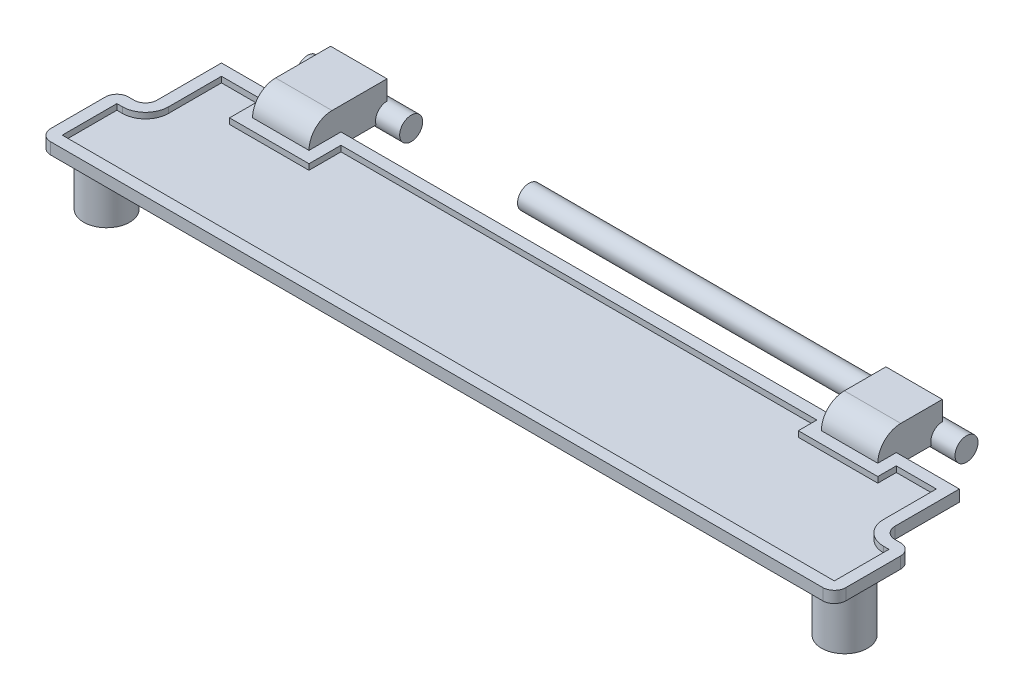
SolidWorks part; units mm, degrees
material "Alloy Steel"
ref_plane "Front Plane" through (0, 0, 0) normal (0, 0, 1) x (1, 0, 0)
ref_plane "Top Plane" through (0, 0, 0) normal (0, 1, 0) x (1, 0, 0)
ref_plane "Right Plane" through (0, 0, 0) normal (1, 0, 0) x (0, 0, -1)
sketch "Sketch1" plane through (0, 0, 0) normal (0, 1, 0) x (1, 0, 0)
  line L0 (0, 0) -> (64.1, 0) construction
  circle A0 centre (64.1, 0) radius 2
  circle A1 centre (0, 0) radius 2
extrude "Boss-Extrude1" add sketch "Sketch1" along normal blind 5
sketch "Sketch2" plane through (0, 5, 0) normal (0, 1, 0) x (1, 0, 0)
  line L0 (0, 0) -> (0, 16.0284) construction
  line L1 (0, 16.0284) -> (64.1, 16.0284) construction
  line L2 (64.1, 16.0284) -> (64.1, -7.5811) construction
  line L3 (0, 3.3731) -> (0, 9.9731)
  line L4 (0, 9.9731) -> (64.1, 9.9731)
  line L5 (64.1, 3.3731) -> (64.1, 9.9731)
  line L6 (66.5854, -3.3731) -> (-2.4854, -3.3731)
  line L7 (66.5854, -3.3731) -> (66.5854, 3.3731)
  line L8 (66.5854, 3.3731) -> (64.1, 3.3731)
  line L9 (-2.4854, -3.3731) -> (-2.4854, 3.3731)
  line L10 (-7.3374, 0) -> (72.8127, 0) construction
  line L12 (0, 3.3731) -> (-2.4854, 3.3731)
  point P4 (32.05, 0)
  point P7 (32.05, 0)
  dimension "D1" = 64.1
extrude "Boss-Extrude3" add sketch "Sketch2" along normal blind 1
fillet "Fillet1" radius 1 6 edges at (0, 5.5, -3.3731) (64.1, 5.5, -3.3731) (66.5854, 5.5, -3.3731) (66.5854, 5.5, 3.3731) (-2.4854, 5.5, 3.3731) (-2.4854, 5.5, -3.3731)
sketch "Sketch3" plane through (0, 6, 0) normal (0, 1, 0) x (1, 0, 0)
  line L0 (32.05, 9.9731) -> (3.43, 9.9731) construction
  line L1 (64.1, 9.9731) -> (0, 9.9731) construction
  line L2 (32.05, 9.9731) -> (60.67, 9.9731) construction
  line L3 (3.43, 9.9731) -> (3.43, 13.9731) construction
  line L4 (3.43, 13.9731) -> (12.43, 13.9731) construction
  line L5 (60.67, 9.9731) -> (60.67, 13.9731) construction
  line L6 (60.67, 13.9731) -> (51.67, 13.9731) construction
  line L7 (7.93, 13.9731) -> (7.93, 7.1953) construction
  line L8 (56.17, 13.9731) -> (56.17, 8.3637) construction
  line L9 (12.43, 13.9731) -> (50.1115, 13.9731) construction
  line L10 (5.48, 7.1953) -> (10.38, 7.1953)
  line L11 (5.48, 7.1953) -> (5.48, 13.9731)
  line L12 (5.48, 13.9731) -> (10.38, 13.9731)
  line L13 (10.38, 7.1953) -> (10.38, 13.9731)
  line L14 (5.48, 7.1953) -> (10.38, 13.9731) construction
  line L15 (5.48, 13.9731) -> (10.38, 7.1953) construction
  line L16 (58.62, 8.3637) -> (53.72, 8.3637)
  line L17 (58.62, 8.3637) -> (58.62, 13.9731)
  line L18 (58.62, 13.9731) -> (53.72, 13.9731)
  line L19 (53.72, 8.3637) -> (53.72, 13.9731)
  line L20 (58.62, 8.3637) -> (53.72, 13.9731) construction
  line L21 (58.62, 13.9731) -> (53.72, 8.3637) construction
  point P13 (7.93, 10.5842)
  point P18 (56.17, 11.1684)
  dimension "D1" = 28.62
extrude "Boss-Extrude4" add sketch "Sketch3" along normal blind 2 and the other way blind 1
sketch "Sketch4" plane through (5.48, 0, 0) normal (-1, 0, 0) x (0, 0, 1)
  line L0 (-13.9731, 5) -> (-13.9731, 8) construction
  circle A0 centre (-13.9731, 5.3165) radius 1
extrude "Boss-Extrude5" add sketch "Sketch4" along normal blind 2 and the other way blind 7
sketch "Sketch5" plane through (53.72, 0, 0) normal (-1, 0, 0) x (0, 0, 1)
  circle A0 centre (-13.9731, 5.3165) radius 1
extrude "Boss-Extrude6" add sketch "Sketch5" along normal blind 31 and the other way blind 7
fillet "Fillet2" radius 2 2 edges at (56.17, 8, -8.3637) (7.93, 8, -7.1953)
fillet "Fillet3" radius 2 rebuild error yes
sketch "Sketch6" plane through (0, 6, 0) normal (0, 1, 0) x (1, 0, 0)
  line L32 (59.62, 7.3637) -> (52.72, 7.3637)
  line L33 (52.72, 7.3637) -> (52.72, 8.9731)
  line L34 (52.72, 8.9731) -> (11.38, 8.9731)
  line L35 (11.38, 8.9731) -> (11.38, 6.1953)
  line L36 (59.62, 7.3637) -> (52.72, 7.3637)
  line L37 (4.48, 6.1953) -> (4.48, 8.9731)
  line L38 (4.48, 8.9731) -> (1, 8.9731)
  line L39 (1, 8.9731) -> (1, 4.3731)
  line L40 (-1, 2.3731) -> (-1.4854, 2.3731)
  line L41 (-1.4854, 2.3731) -> (-1.4854, -2.3731)
  line L42 (-1.4854, -2.3731) -> (65.5854, -2.3731)
  line L43 (65.5854, -2.3731) -> (65.5854, 2.3731)
  line L44 (65.5854, 2.3731) -> (65.1, 2.3731)
  line L45 (63.1, 4.3731) -> (63.1, 8.9731)
  line L46 (63.1, 8.9731) -> (59.62, 8.9731)
  line L47 (59.62, 8.9731) -> (59.62, 7.3637)
  line L48 (11.38, 6.1953) -> (4.48, 6.1953)
  line L49 (52.72, 7.3637) -> (52.72, 8.9731)
  line L50 (52.72, 8.9731) -> (11.38, 8.9731)
  line L51 (11.38, 8.9731) -> (11.38, 6.1953)
  line L52 (11.38, 6.1953) -> (4.48, 6.1953)
  line L53 (4.48, 6.1953) -> (4.48, 8.9731)
  line L54 (4.48, 8.9731) -> (1, 8.9731)
  line L55 (1, 8.9731) -> (1, 4.3731)
  line L56 (-1, 2.3731) -> (-1.4854, 2.3731)
  line L57 (-1.4854, 2.3731) -> (-1.4854, -2.3731)
  line L58 (-1.4854, -2.3731) -> (65.5854, -2.3731)
  line L59 (65.5854, -2.3731) -> (65.5854, 2.3731)
  line L60 (65.5854, 2.3731) -> (65.1, 2.3731)
  line L61 (63.1, 4.3731) -> (63.1, 8.9731)
  line L62 (63.1, 8.9731) -> (59.62, 8.9731)
  line L63 (59.62, 8.9731) -> (59.62, 7.3637)
  arc A12 (-1, 2.3731) -> (1, 4.3731) centre (-1, 4.3731) ccw
  arc A13 (63.1, 4.3731) -> (65.1, 2.3731) centre (65.1, 4.3731) ccw
  arc A14 (-1, 2.3731) -> (1, 4.3731) centre (-1, 4.3731) ccw
  arc A15 (63.1, 4.3731) -> (65.1, 2.3731) centre (65.1, 4.3731) ccw
  dimension "D1" = 1
extrude "Cut-Extrude1" cut sketch "Sketch6" against normal blind 0.5
fillet "Fillet4" radius 2 rebuild error yes
equation "\"2.1.00mm\"=3"
